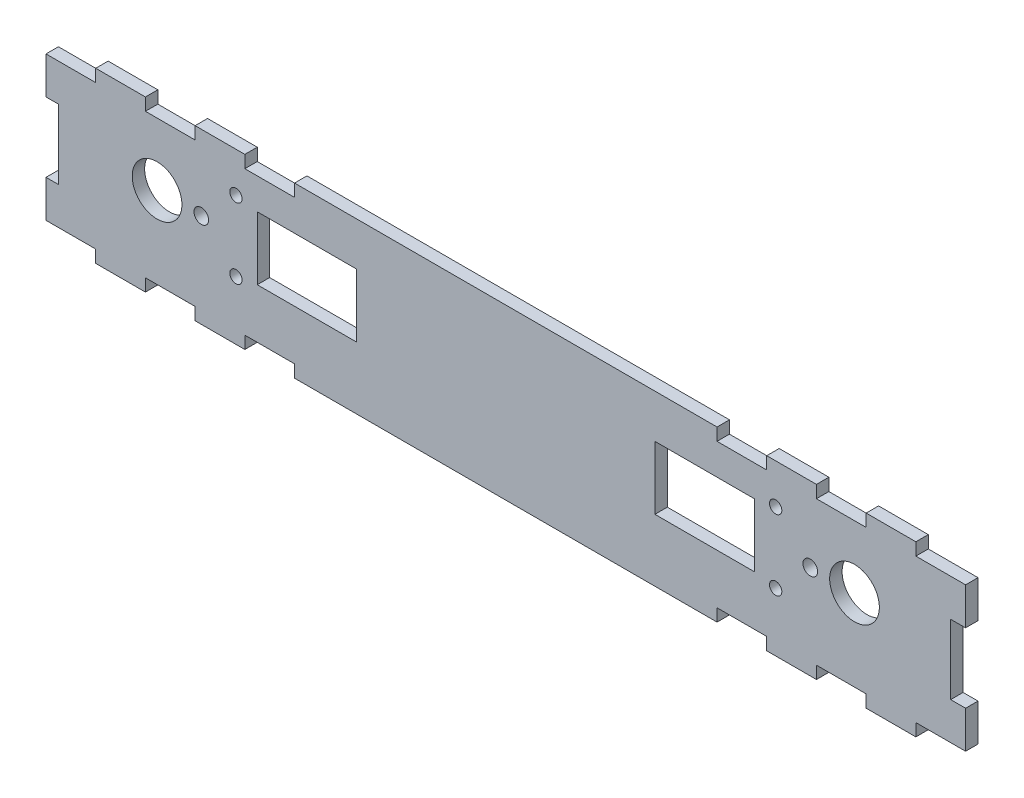
SolidWorks part; units mm, degrees
material "Acrylic (Medium-high impact)"
ref_plane "Front Plane" through (0, 0, 0) normal (0, 0, 1) x (1, 0, 0)
ref_plane "Top Plane" through (0, 0, 0) normal (0, 1, 0) x (1, 0, 0)
ref_plane "Right Plane" through (0, 0, 0) normal (1, 0, 0) x (0, 0, -1)
sketch "Sketch3" plane through (0, 0, 0) normal (0, 0, 1) x (1, 0, 0)
  line L0 (0, 22.5) -> (0, 0)
  line L1 (0, 0) -> (31.6, 0)
  line L2 (36.6, 5) -> (36.6, 17.5)
  line L3 (31.6, 22.5) -> (0, 22.5)
  line L4 (0, 0) -> (-63.5, 0) construction
  line L5 (-63.5, 0) -> (-63.5, 28.85) construction
  line L6 (-158.6, 22.5) -> (-127, 22.5)
  line L7 (0, 22.5) -> (-25.4, 22.5)
  line L8 (0, 22.5) -> (0, 0)
  line L9 (0, 0) -> (-25.4, 0)
  line L10 (-25.4, 22.5) -> (-25.4, 0)
  line L11 (-163.6, 5) -> (-163.6, 17.5)
  line L12 (-127, 0) -> (-158.6, 0)
  line L13 (-127, 22.5) -> (-127, 0)
  line L14 (-127, 0) -> (-101.6, 0)
  line L15 (-101.6, 22.5) -> (-101.6, 0)
  line L16 (-127, 22.5) -> (-101.6, 22.5)
  line L17 (-127, 22.5) -> (-127, 0)
  line L18 (-180.975, 28.85) -> (-180.975, -6.3925)
  line L21 (20.8125, -11.155) -> (58.7375, -11.155)
  line L22 (58.7375, 0) -> (58.7375, -11.155)
  line L25 (-179.3875, 28.85) -> (-185.7375, 28.85)
  line L26 (-185.7375, 22.5) -> (-185.7375, 28.85)
  line L27 (-185.7375, 28.85) -> (58.7375, 28.85)
  line L28 (-185.7375, 28.85) -> (-185.7375, -11.155)
  line L29 (-185.7375, -11.155) -> (58.7375, -11.155)
  line L30 (58.7375, 28.85) -> (58.7375, -11.155)
  line L31 (-180.975, -6.3925) -> (58.7375, -6.3925)
  line L32 (-185.7375, 24.0875) -> (53.975, 24.0875)
  line L33 (53.975, 24.0875) -> (53.975, -11.155)
  line L35 (-127, 22.5) -> (-101.6, 22.5)
  line L36 (-127, 22.5) -> (-127, 19.325)
  line L37 (-127, 19.325) -> (-101.6, 19.325)
  line L38 (-101.6, 22.5) -> (-101.6, 19.325)
  line L39 (-127, 0) -> (-101.6, 0)
  line L40 (-127, 0) -> (-127, 3.175)
  line L41 (-127, 3.175) -> (-101.6, 3.175)
  line L42 (-101.6, 0) -> (-101.6, 3.175)
  line L43 (0, 22.5) -> (-25.4, 22.5)
  line L44 (0, 22.5) -> (0, 19.325)
  line L45 (0, 19.325) -> (-25.4, 19.325)
  line L46 (-25.4, 22.5) -> (-25.4, 19.325)
  line L47 (0, 0) -> (-25.4, 0)
  line L48 (0, 0) -> (0, 3.175)
  line L49 (0, 3.175) -> (-25.4, 3.175)
  line L50 (-25.4, 0) -> (-25.4, 3.175)
  circle A2 centre (5.45, 2.25) radius 1.575
  circle A3 centre (5.45, 20.25) radius 1.575
  arc A6 (31.6, 0) -> (36.6, 5) centre (31.6, 5) ccw
  arc A7 (36.6, 17.5) -> (31.6, 22.5) centre (31.6, 17.5) ccw
  arc A8 (19.25, 11.25) -> (31.95, 11.25) centre (25.6, 11.25) ccw
  arc A9 (31.95, 11.25) -> (19.25, 11.25) centre (25.6, 11.25) ccw
  arc A10 (12.425, 11.25) -> (16.175, 11.25) centre (14.3, 11.25) ccw
  arc A11 (16.175, 11.25) -> (12.425, 11.25) centre (14.3, 11.25) ccw
  arc A12 (-143.175, 11.25) -> (-139.425, 11.25) centre (-141.3, 11.25) cw
  arc A13 (-139.425, 11.25) -> (-143.175, 11.25) centre (-141.3, 11.25) cw
  arc A14 (-158.95, 11.25) -> (-146.25, 11.25) centre (-152.6, 11.25) cw
  arc A15 (-146.25, 11.25) -> (-158.95, 11.25) centre (-152.6, 11.25) cw
  arc A16 (-163.6, 17.5) -> (-158.6, 22.5) centre (-158.6, 17.5) cw
  arc A17 (-158.6, 0) -> (-163.6, 5) centre (-158.6, 5) cw
  circle A18 centre (-132.45, 20.25) radius 1.575
  circle A19 centre (-132.45, 2.25) radius 1.575
  dimension "D3" = 5.45
  dimension "D4" = 3.15
  dimension "D8" = 3.15
  dimension "D6" = 2.25
  dimension "D9" = 1.875
  dimension "D10" = 4.7625
  dimension "D11" = 6.35
  dimension "D12" = 4.7625
  dimension "D17" = 5
  dimension "D18" = 5
  dimension "D1" = 31.6
  dimension "D2" = 36.6
  dimension "D5" = 2.25
  dimension "D7" = 5.45
  dimension "D13" = 11.25
  dimension "D14" = 14.3
  dimension "D15" = 11
  dimension "D16" = 11.25
  dimension "D19" = 22.5
  dimension "D20" = 244.475
  dimension "D21" = 30.48
  dimension "D22" = 25.4
  dimension "D23" = 3.175
  dimension "D24" = 25.4
  dimension "D25" = 3.175
  dimension "D26" = 25.4
extrude "Boss-Extrude1" add sketch "Sketch3" along normal blind 3.175 contours L33 L32 L18 L31 A7 L2 A6 L1 L9 L10 L7 L3 L12 A17 L11 A16 L6 L16 L15 L14 | A17 L12 L13 L6 A16 L11 A18 A12 A13 A14 A15 A19 | L2 A7 L3 L0 L1 A6 A11 A10 A9 A8 A2 A3 | L0 L49 L10 L9 | L45 L0 L7 L10 | L13 L37 L15 L16 | L40 L41 L42 L39 region at (16.9888, 11.25, 0) region at (-12.7, 20.9125, 0) region at (-12.7, 1.5875, 0) region at (-143.9888, 11.25, 0) region at (-114.3, 20.9125, 0) region at (-63.5, 7.3333, 0)
sketch "Sketch4" plane through (0, 0, 3.175) normal (0, 0, 1) x (1, 0, 0)
  line L0 (-155.575, 30.4375) -> (-155.575, 27.2625)
  line L1 (-180.975, 24.0875) -> (53.975, 24.0875)
  line L2 (-180.975, 24.0875) -> (-180.975, 30.4375)
  line L3 (-180.975, 30.4375) -> (53.975, 30.4375)
  line L4 (53.975, -6.3925) -> (53.975, 24.0875)
  line L5 (53.975, 24.0875) -> (-180.975, 24.0875)
  line L6 (-180.975, 24.0875) -> (-180.975, -6.3925)
  line L7 (-180.975, -6.3925) -> (53.975, -6.3925)
  line L8 (53.975, -6.3925) -> (53.975, 24.0875)
  line L9 (53.975, 24.0875) -> (-180.975, 24.0875)
  line L10 (-180.975, 24.0875) -> (-180.975, -6.3925)
  line L11 (-180.975, -6.3925) -> (53.975, -6.3925)
  line L12 (53.975, 24.0875) -> (53.975, 30.4375)
  line L13 (-180.975, 30.4375) -> (53.975, 30.4375)
  line L14 (-180.975, 30.4375) -> (-180.975, 27.2625)
  line L15 (-180.975, 27.2625) -> (53.975, 27.2625)
  line L16 (53.975, 30.4375) -> (53.975, 27.2625)
  line L17 (-180.975, 30.4375) -> (-168.275, 30.4375)
  line L18 (-180.975, 30.4375) -> (-180.975, 27.2625)
  line L19 (-180.975, 27.2625) -> (-168.275, 27.2625)
  line L20 (-168.275, 30.4375) -> (-168.275, 27.2625)
  line L21 (-155.575, 30.4375) -> (-142.875, 30.4375)
  line L22 (-142.875, 30.4375) -> (-142.875, 27.2625)
  line L23 (-155.575, 27.2625) -> (-142.875, 27.2625)
  line L24 (-130.175, 30.4375) -> (-130.175, 27.2625)
  line L25 (-130.175, 30.4375) -> (-117.475, 30.4375)
  line L26 (-117.475, 30.4375) -> (-117.475, 27.2625)
  line L27 (-130.175, 27.2625) -> (-117.475, 27.2625)
  line L28 (28.575, 27.2625) -> (28.575, 30.4375)
  line L29 (53.975, 27.2625) -> (41.275, 27.2625)
  line L30 (53.975, 27.2625) -> (53.975, 30.4375)
  line L31 (53.975, 30.4375) -> (41.275, 30.4375)
  line L32 (41.275, 27.2625) -> (41.275, 30.4375)
  line L33 (28.575, 27.2625) -> (15.875, 27.2625)
  line L34 (15.875, 27.2625) -> (15.875, 30.4375)
  line L35 (28.575, 30.4375) -> (15.875, 30.4375)
  line L36 (3.175, 27.2625) -> (3.175, 30.4375)
  line L37 (3.175, 27.2625) -> (-9.525, 27.2625)
  line L38 (-9.525, 27.2625) -> (-9.525, 30.4375)
  line L39 (3.175, 30.4375) -> (-9.525, 30.4375)
  line L40 (-180.975, 8.8475) -> (49.4654, 8.8475) construction
  line L41 (3.175, -12.7425) -> (-9.525, -12.7425)
  line L42 (-9.525, -9.5675) -> (-9.525, -12.7425)
  line L43 (3.175, -9.5675) -> (-9.525, -9.5675)
  line L44 (3.175, -9.5675) -> (3.175, -12.7425)
  line L45 (28.575, -12.7425) -> (15.875, -12.7425)
  line L46 (15.875, -9.5675) -> (15.875, -12.7425)
  line L47 (28.575, -9.5675) -> (15.875, -9.5675)
  line L48 (41.275, -9.5675) -> (41.275, -12.7425)
  line L49 (53.975, -12.7425) -> (41.275, -12.7425)
  line L50 (53.975, -9.5675) -> (53.975, -12.7425)
  line L51 (53.975, -9.5675) -> (41.275, -9.5675)
  line L52 (28.575, -9.5675) -> (28.575, -12.7425)
  line L53 (-130.175, -9.5675) -> (-117.475, -9.5675)
  line L54 (-117.475, -12.7425) -> (-117.475, -9.5675)
  line L55 (-130.175, -12.7425) -> (-117.475, -12.7425)
  line L56 (-130.175, -12.7425) -> (-130.175, -9.5675)
  line L57 (-155.575, -9.5675) -> (-142.875, -9.5675)
  line L58 (-142.875, -12.7425) -> (-142.875, -9.5675)
  line L59 (-155.575, -12.7425) -> (-142.875, -12.7425)
  line L60 (-168.275, -12.7425) -> (-168.275, -9.5675)
  line L61 (-180.975, -9.5675) -> (-168.275, -9.5675)
  line L62 (-180.975, -12.7425) -> (-180.975, -9.5675)
  line L63 (-180.975, -12.7425) -> (-168.275, -12.7425)
  line L64 (53.975, -12.7425) -> (53.975, -9.5675)
  line L65 (-180.975, -9.5675) -> (53.975, -9.5675)
  line L66 (-180.975, -12.7425) -> (-180.975, -9.5675)
  line L67 (-180.975, -12.7425) -> (53.975, -12.7425)
  line L68 (53.975, -6.3925) -> (53.975, -12.7425)
  line L69 (53.975, -6.3925) -> (-180.975, -6.3925)
  line L70 (-180.975, -12.7425) -> (53.975, -12.7425)
  line L71 (-180.975, -6.3925) -> (-180.975, -12.7425)
  line L72 (-180.975, -6.3925) -> (53.975, -6.3925)
  line L73 (-155.575, -12.7425) -> (-155.575, -9.5675)
  line M29 (53.975, 24.0875) -> (-180.975, 24.0875)
  line M31 (-180.975, -6.3925) -> (53.975, -6.3925)
  dimension "D2" = 6.35
  dimension "D3" = 3.175
  dimension "D4" = 12.7
  dimension "D5" = 3
  dimension "D6" = 12.7
  dimension "D7" = 3
  dimension "D1" = 0
extrude "Boss-Extrude2" add sketch "Sketch4" against normal blind 3.175 contours L15 L38 L13 L26 | L24 L13 L22 L15 | L13 L20 L15 L0 | L15 L2 L12 M29 | L36 L15 L34 L3 | L15 L32 L3 L28 | L71 L61 L65 L57 L53 L43 L47 L51 L68 M31 | L52 L67 L48 L65 | L44 L67 L46 L65 | L54 L67 L42 L65 | L58 L67 L56 L65 | L67 L73 L65 L60 region at (-161.925, 28.85, 3.175) region at (-63.5, 25.675, 3.175) region at (-136.525, 28.85, 3.175) region at (-63.5, 28.85, 3.175) region at (-63.5, -7.98, 3.175) region at (9.525, 28.85, 3.175) region at (34.925, 28.85, 3.175) region at (-161.925, -11.155, 3.175) region at (34.925, -11.155, 3.175) region at (-136.525, -11.155, 3.175) region at (9.525, -11.155, 3.175) region at (-63.5, -11.155, 3.175)
sketch "Sketch5" plane through (0, 0, 3.175) normal (0, 0, 1) x (1, 0, 0)
  line L0 (53.975, 27.2625) -> (53.975, -9.5675) construction
  line L1 (-168.275, -12.7425) -> (-180.975, -12.7425)
  line L2 (-168.275, -12.7425) -> (-168.275, -0.0425)
  line L3 (-168.275, -0.0425) -> (-180.975, -0.0425)
  line L4 (-180.975, -12.7425) -> (-180.975, -0.0425)
  line L5 (-180.975, 27.2625) -> (-180.975, -9.5675) construction
  line L6 (-168.275, 30.4375) -> (-180.975, 30.4375)
  line L7 (-168.275, 30.4375) -> (-168.275, 17.7375)
  line L8 (-168.275, 17.7375) -> (-180.975, 17.7375)
  line L9 (-180.975, 30.4375) -> (-180.975, 17.7375)
  line L10 (41.275, 30.4375) -> (53.975, 30.4375)
  line L11 (41.275, 30.4375) -> (41.275, 17.7375)
  line L12 (41.275, 17.7375) -> (53.975, 17.7375)
  line L13 (53.975, 30.4375) -> (53.975, 17.7375)
  line L15 (41.275, -12.7425) -> (53.975, -12.7425)
  line L16 (41.275, -12.7425) -> (41.275, -0.0425)
  line L17 (41.275, -0.0425) -> (53.975, -0.0425)
  line L18 (53.975, -12.7425) -> (53.975, -0.0425)
  line L19 (-180.975, 17.7375) -> (-177.8, 17.7375)
  line L20 (-180.975, 17.7375) -> (-180.975, -0.0425)
  line L21 (-180.975, -0.0425) -> (-177.8, -0.0425)
  line L22 (-177.8, 17.7375) -> (-177.8, -0.0425)
  line L23 (53.975, 17.7375) -> (50.165, 17.7375)
  line L24 (53.975, 17.7375) -> (53.975, -0.0425)
  line L25 (53.975, -0.0425) -> (50.165, -0.0425)
  line L26 (50.165, 17.7375) -> (50.165, -0.0425)
  dimension "D1" = 12.7
  dimension "D2" = 12.7
  dimension "D3" = 12.7
  dimension "D4" = 3.175
  dimension "D5" = 3.81
extrude "Cut-Extrude1" cut sketch "Sketch5" against normal blind 7.62 contours L22 L8 L20 L3 | L12 L26 L17 L24 region at (-179.3875, 8.8475, 3.175) region at (52.07, 8.8475, 3.175)
